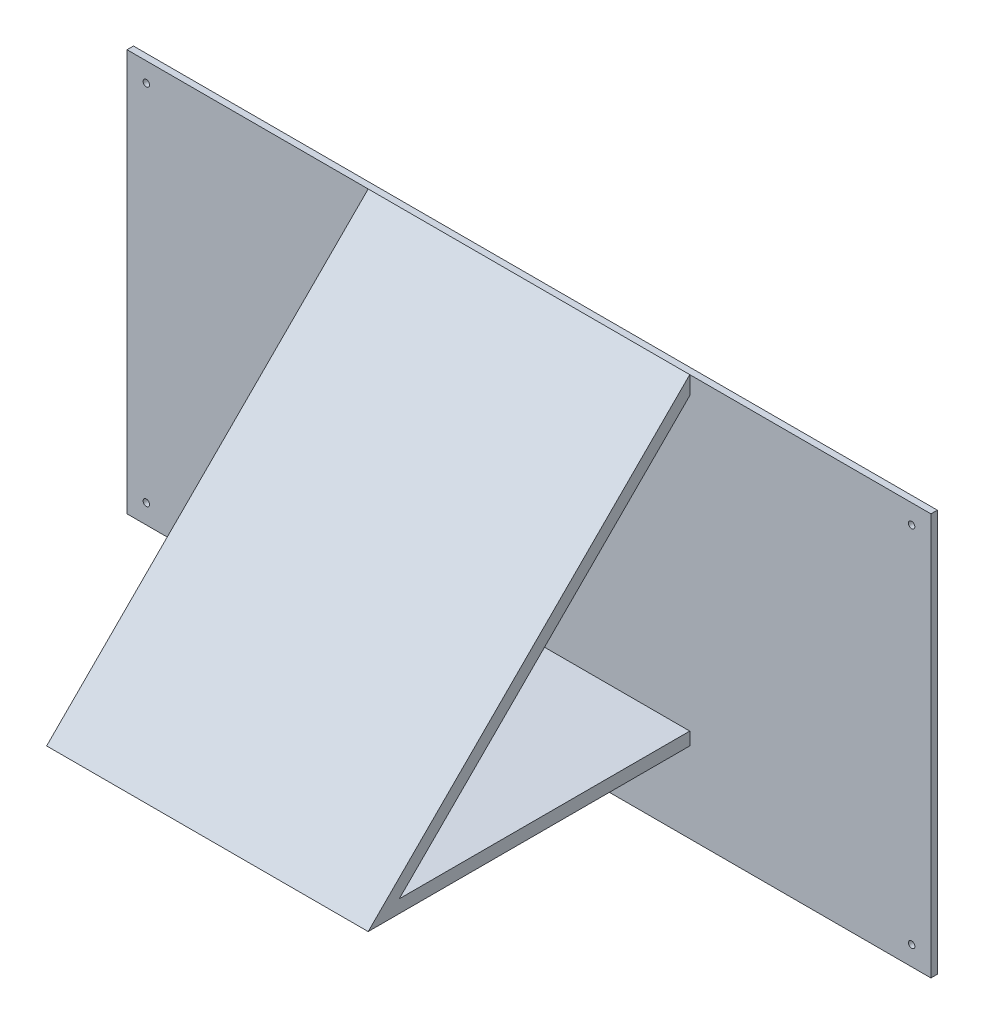
SolidWorks part; units mm, degrees
ref_plane "Ebene vorne" through (0, 0, 0) normal (0, 0, 1) x (1, 0, 0)
ref_plane "Ebene oben" through (0, 0, 0) normal (0, 1, 0) x (1, 0, 0)
ref_plane "Ebene rechts" through (0, 0, 0) normal (1, 0, 0) x (0, 0, -1)
sketch "Skizze1" plane through (0, 0, 0) normal (0, 0, 1) x (1, 0, 0)
  line L1 (0, 125) -> (250, 125)
  line L2 (0, 125) -> (0, 0)
  line L3 (0, 0) -> (250, 0)
  line L4 (250, 125) -> (250, 0)
  dimension "D1" = 250
  dimension "D2" = 125
extrude "Aufsatz-Linear austragen1" add sketch "Skizze1" along normal blind 2 contours L2 L1 L4 L3
sketch "Skizze2" plane through (0, 0, 2) normal (0, 0, 1) x (1, 0, 0)
  line L0 (75, 75) -> (0, 75) construction
  line L1 (75, 125) -> (175, 125)
  line L2 (75, 125) -> (75, 25)
  line L3 (75, 25) -> (175, 25)
  line L4 (175, 125) -> (175, 25)
  line L5 (0, 125) -> (0, 0) construction
  line L6 (175, 75) -> (250, 75) construction
  line L7 (250, 125) -> (250, 0) construction
  line L8 (0, 125) -> (250, 125) construction
  dimension "D1" = 100
  dimension "D2" = 100
extrude "Aufsatz-Linear austragen2" add sketch "Skizze2" along normal blind 100
sketch "Skizze3" plane through (75, 0, 0) normal (-1, 0, 0) x (0, 0, 1)
  line L0 (102, 25) -> (102, 125)
  line L1 (102, 125) -> (2, 125)
  line L2 (2, 125) -> (102, 25)
extrude "Schnitt-Linear austragen1" cut sketch "Skizze3" against normal blind 100
sketch "Skizze4" plane through (75, 0, 0) normal (-1, 0, 0) x (0, 0, 1)
  line L0 (2, 119.3431) -> (92.3431, 29)
  line L1 (92.3431, 29) -> (2, 29)
  line L2 (2, 29) -> (2, 119.3431)
  line L3 (2, 125) -> (102, 25) construction
  line L5 (102, 25) -> (2, 25) construction
  line L6 (2, 125) -> (2, 25) construction
  dimension "D1" = 4
  dimension "D3" = 4
extrude "Schnitt-Linear austragen2" cut sketch "Skizze4" against normal blind 100 contours L2 L0 L1
sketch "Skizze6" plane through (0, 0, 0) normal (0, 0, -1) x (-1, 0, 0)
  line L0 (0, 125) -> (-250, 125) construction
  line L1 (-246, 121) -> (-4, 121)
  line L2 (-246, 121) -> (-246, 4)
  line L3 (-246, 4) -> (-4, 4)
  line L4 (-4, 121) -> (-4, 4)
  line L5 (-250, 125) -> (-250, 0) construction
  line L6 (0, 0) -> (-250, 0) construction
  line L7 (0, 125) -> (0, 0) construction
  dimension "D1" = 4
  dimension "D2" = 4
  dimension "D3" = 4
  dimension "D4" = 4
extrude "Aufsatz-Linear austragen3" add sketch "Skizze6" along normal blind 2
sketch "Skizze7" plane through (0, 0, -2) normal (0, 0, -1) x (-1, 0, 0)
  line L0 (-4, 121) -> (-246, 121) construction
  line L1 (-246, 121) -> (-246, 4) construction
  line L2 (-246, 4) -> (-4, 4) construction
  line L3 (-4, 4) -> (-4, 121) construction
  line L4 (-246, 4) -> (-4, 4) construction
  line L5 (-4, 4) -> (-4, 121) construction
  circle A0 centre (-244, 119) radius 1
  circle A1 centre (-6, 6) radius 1
  circle A2 centre (-6, 119) radius 1
  circle A3 centre (-244, 6) radius 1
  point P2 (-243.1589, 118.0899)
  point P9 (-134.757, 103.3576)
  point P14 (-8.7705, 7.3312)
  point P15 (-175.5564, 116.2895)
  point P16 (-6.4379, 118.3574)
  dimension "D1" = 2
  dimension "D2" = 2
  dimension "D3" = 2
  dimension "D4" = 2
  dimension "D5" = 2
  dimension "D6" = 2
  dimension "D7" = 2
  dimension "D8" = 2
extrude "Schnitt-Linear austragen5" cut sketch "Skizze7" against normal blind 32
